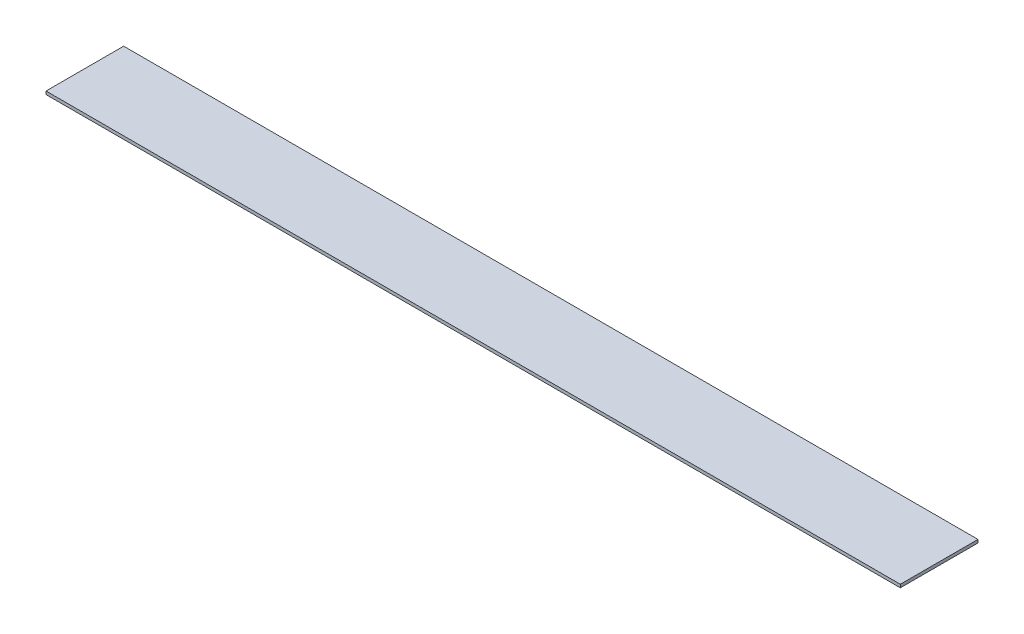
SolidWorks part; units mm, degrees
material "Cast Alloy Steel"
ref_plane "Front Plane" through (0, 0, 0) normal (0, 0, 1) x (1, 0, 0)
ref_plane "Top Plane" through (0, 0, 0) normal (0, 1, 0) x (1, 0, 0)
ref_plane "Right Plane" through (0, 0, 0) normal (1, 0, 0) x (0, 0, -1)
sketch "Sketch1" plane through (0, 0, 0) normal (0, 1, 0) x (1, 0, 0)
  line L1 (-34.925, -3.175) -> (34.925, -3.175)
  line L2 (-34.925, -3.175) -> (-34.925, 3.175)
  line L3 (-34.925, 3.175) -> (34.925, 3.175)
  line L4 (34.925, -3.175) -> (34.925, 3.175)
  line L5 (-34.925, -3.175) -> (34.925, 3.175) construction
  line L6 (-34.925, 3.175) -> (34.925, -3.175) construction
  point P0 (0, 0)
  dimension "D1" = 69.85
  dimension "D2" = 6.35
extrude "Boss-Extrude1" add sketch "Sketch1" along normal blind 0.254
